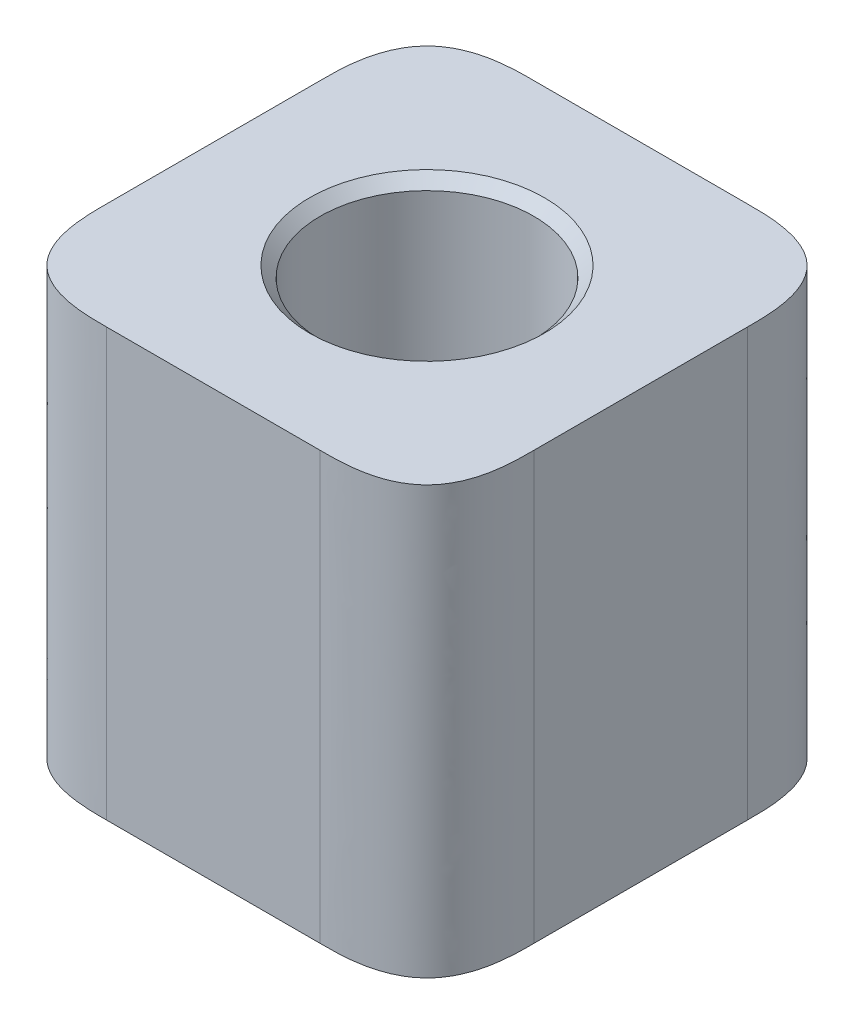
SolidWorks part; units mm, degrees
ref_plane "Front Plane" through (0, 0, 0) normal (0, 0, 1) x (1, 0, 0)
ref_plane "Top Plane" through (0, 0, 0) normal (0, 1, 0) x (1, 0, 0)
ref_plane "Right Plane" through (0, 0, 0) normal (1, 0, 0) x (0, 0, -1)
sketch "Sketch2" plane through (0, 0, 0) normal (0, 1, 0) x (1, 0, 0)
  line L0 (-5.3774, 2) -> (4.3662, 2) construction
  line L1 (-4, -4) -> (4, -4)
  line L2 (-4, -4) -> (-4, 4)
  line L3 (-4, 4) -> (4, 4)
  line L4 (4, -4) -> (4, 4)
  line L5 (-4, -4) -> (4, 4) construction
  line L6 (-4, 4) -> (4, -4) construction
  circle A0 centre (0, 0) radius 2
  dimension "D1" = 4
  dimension "D2" = 2
extrude "Boss-Extrude1" add sketch "Sketch2" along normal blind 7
sketch "Sketch3" plane through (0, 0, 0) normal (0, -1, 0) x (1, 0, 0)
  line L1 (-4, 4) -> (4, 4)
  line L2 (-4, 4) -> (-4, -4)
  line L3 (-4, -4) -> (4, -4)
  line L4 (4, 4) -> (4, -4)
extrude "Boss-Extrude2" add sketch "Sketch3" along normal blind 1
fillet "Fillet1" radius 2 4 edges at (4, 3, 4) (-4, 3, 4) (-4, 3, -4) (4, 3, -4)
hole_wizard "CSK for M2 Flat Head Machine Screw1" positions "Sketch5" profile "Sketch6" countersink size "M2" standard "ANSI Metric"
sketch "Sketch5" plane through (0, 7, 0) normal (0, 1, 0) x (1, 0, 0)
  point P0 (0, 0)
sketch "Sketch6" plane through (0, 7, 0) normal (1, 0, 0) x (0, 0, 1)
  line L0 (0, 0) -> (0, 7.721)
  line L1 (0, 7.721) -> (1.2, 7)
  line L2 (1.2, 7) -> (1.2, 1)
  line L3 (1.2, 1) -> (2.2, 0)
  line L5 (2.2, 0) -> (0, 0)
  line L6 (-1.2, 1) -> (-2.2, 0) construction
  line L10 (0, 7.721) -> (-1.2, 7) construction
  line L11 (0, -6.35) -> (0, 107.95) construction
  dimension "Hole Dia." = 2.4
  dimension "Hole Depth" = 7
  dimension "Near C'Sink Dia." = 4.4
  dimension "Near C'Sink Angle" = 90
  dimension "Drill Angle" = 118
